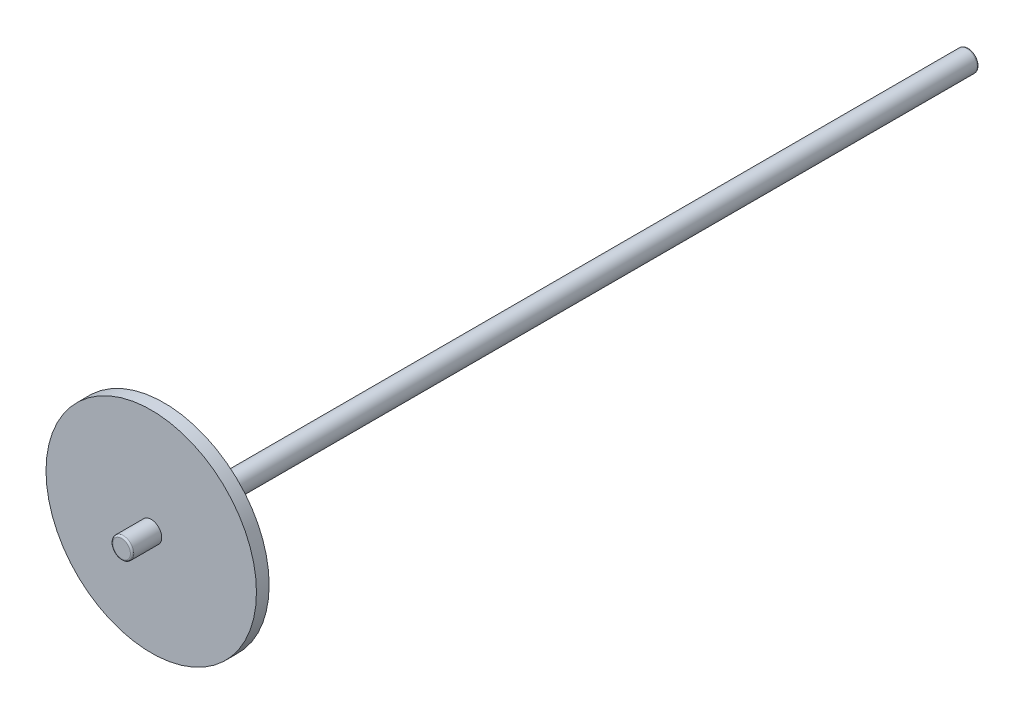
SolidWorks part; units mm, degrees
ref_plane "Plano frontal" through (0, 0, 0) normal (0, 0, 1) x (1, 0, 0)
ref_plane "Plano superior" through (0, 0, 0) normal (0, 1, 0) x (1, 0, 0)
ref_plane "Plano direito" through (0, 0, 0) normal (1, 0, 0) x (0, 0, -1)
ref_plane "Plano2" through (0, 0, 5) normal (0, 0, 1) x (1, 0, 0)
sketch "Esboço1" plane through (0, 0, 0) normal (0, 0, 1) x (1, 0, 0)
  circle A0 centre (0, 0) radius 12.425
  circle A1 centre (0, 0) radius 1.2415
  dimension "D1" = 24.85
  dimension "D2" = 2.483
extrude "Ressalto-extrusão1" add sketch "Esboço1" along normal blind 1.5
sketch "Esboço2" plane through (0, 0, 0) normal (0, 0, 1) x (1, 0, 0)
  circle A0 centre (0, 0) radius 1.2415
  circle A1 centre (0, 0) radius 2.2
  dimension "D1" = 4.4
extrude "Ressalto-extrusão2" add sketch "Esboço2" against normal blind 1
ref_plane "Plano1" through (0, 0, 16.5) normal (0, 0, 1) x (1, 0, 0)
sketch "Esboço3" plane through (0, 0, 5) normal (0, 0, 1) x (1, 0, 0)
  circle A0 centre (0, 0) radius 1.2415
extrude "Ressalto-extrusão3" add sketch "Esboço3" against normal blind 100
fillet "Filete1" radius 0.2 2 edges at (1.2415, 0, -95) (1.2415, 0, 5)
